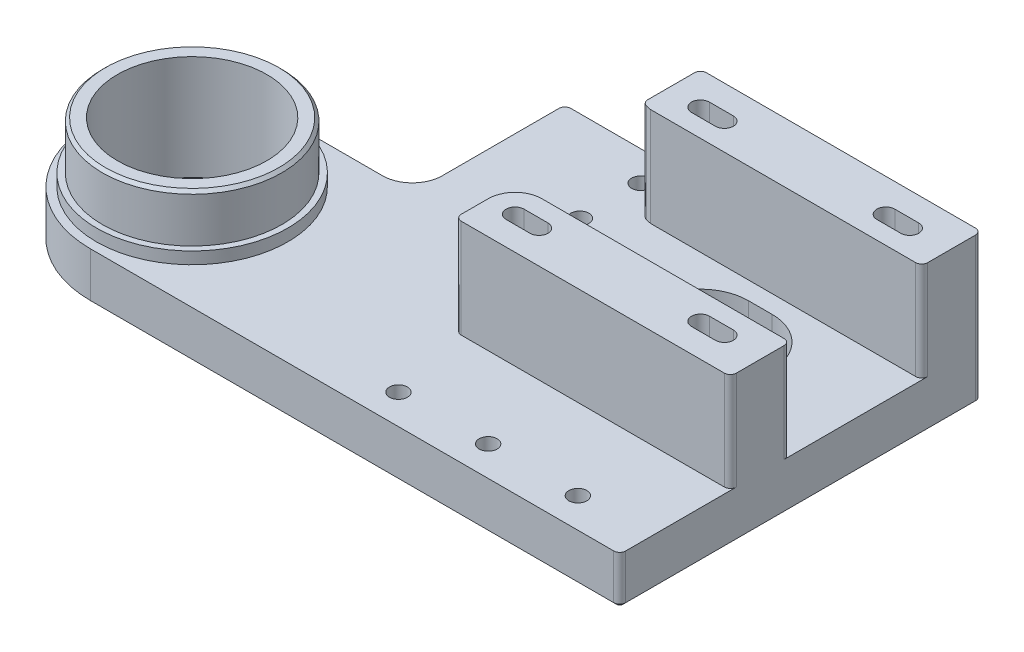
SolidWorks part; units mm, degrees
ref_plane "Front Plane" through (0, 0, 0) normal (0, 0, 1) x (1, 0, 0)
ref_plane "Top Plane" through (0, 0, 0) normal (0, 1, 0) x (1, 0, 0)
ref_plane "Right Plane" through (0, 0, 0) normal (1, 0, 0) x (0, 0, -1)
sketch "Sketch1" plane through (0, 0, 0) normal (0, 1, 0) x (1, 0, 0)
  line L0 (60.6181, 17.7752) -> (49.3328, 24.1377) construction
  line L2 (-17.5, 17.5) -> (-17.5, -17.5)
  line L5 (47.5, 37.5) -> (78.5, 37.5) construction
  line L6 (47.5, 37.5) -> (47.5, 6.5) construction
  line L7 (47.5, 6.5) -> (78.5, 6.5) construction
  line L8 (78.5, 37.5) -> (78.5, 6.5) construction
  line L9 (64.0945, 26.7249) -> (9.1398, 39.4552) construction
  line L10 (42.2652, 20.3799) -> (40.3703, -3.2389) construction
  line L11 (63, 22) -> (63, 43) construction
  line L12 (84, 43) -> (42, 43) construction
  line L13 (84, 43) -> (84, 1) construction
  line L14 (84, 1) -> (42, 1) construction
  line L15 (42, 43) -> (42, 1) construction
  line L16 (63, 22) -> (84, 22) construction
  line L17 (-12.5, -1000) -> (-12.5, 49000) construction
  line L18 (-1001.6818, 12.5) -> (48998.3182, 12.5) construction
  line L19 (-991.5, -12.5) -> (49008.5, -12.5) construction
  line L20 (-17.5, -17.5) -> (89, -17.5)
  line L21 (89, 43) -> (89, -17.5)
  line L23 (47.5, 37.5) -> (51.5, 37.5) construction
  line L24 (47.5, 39) -> (51.5, 39)
  line L25 (47.5, 36) -> (51.5, 36)
  line L26 (78.5, 37.5) -> (82.5, 37.5) construction
  line L27 (78.5, 39) -> (82.5, 39)
  line L28 (78.5, 36) -> (82.5, 36)
  line L29 (47.5, 6.5) -> (51.5, 6.5) construction
  line L30 (47.5, 8) -> (51.5, 8)
  line L31 (47.5, 5) -> (51.5, 5)
  line L32 (78.5, 6.5) -> (82.5, 6.5) construction
  line L33 (78.5, 8) -> (82.5, 8)
  line L34 (78.5, 5) -> (82.5, 5)
  line L35 (63, 22) -> (67, 22) construction
  line L36 (63, 30) -> (67, 30)
  line L37 (63, 14) -> (67, 14)
  line L40 (-17.5, 17.5) -> (19.3317, 17.5)
  line L41 (19.3317, 17.5) -> (19.3317, 43)
  line L42 (19.3317, 43) -> (89, 43)
  line L43 (84, -966.1083) -> (84, 49033.8917) construction
  line L44 (19.3317, 43) -> (-79.4, 43) construction
  line L45 (19.3317, 38) -> (89, 38) construction
  circle A0 centre (0, 0) radius 21 construction
  circle A1 centre (47.5, 37.5) radius 1.5 construction
  circle A2 centre (78.5, 37.5) radius 1.5 construction
  circle A3 centre (78.5, 6.5) radius 1.5 construction
  circle A4 centre (47.5, 6.5) radius 1.5 construction
  circle A5 centre (63, 22) radius 8 construction
  circle A9 centre (47, 20) radius 1.425
  circle A10 centre (47, 20) radius 6.5 construction
  circle A11 centre (0, 0) radius 42 construction
  arc A12 (40.3703, -3.2389) -> (9.1398, 39.4552) centre (0, 0) cw construction
  arc A13 (42.2652, 20.3799) -> (49.3328, 24.1377) centre (47, 20) cw construction
  arc A14 (64.0945, 26.7249) -> (60.6181, 17.7752) centre (63, 22) cw construction
  circle A15 centre (63, 22) radius 7 construction
  arc A16 (47.5, 39) -> (47.5, 36) centre (47.5, 37.5) ccw
  arc A17 (51.5, 36) -> (51.5, 39) centre (51.5, 37.5) ccw
  arc A18 (78.5, 39) -> (78.5, 36) centre (78.5, 37.5) ccw
  arc A19 (82.5, 36) -> (82.5, 39) centre (82.5, 37.5) ccw
  arc A20 (47.5, 8) -> (47.5, 5) centre (47.5, 6.5) ccw
  arc A21 (51.5, 5) -> (51.5, 8) centre (51.5, 6.5) ccw
  arc A22 (78.5, 8) -> (78.5, 5) centre (78.5, 6.5) ccw
  arc A23 (82.5, 5) -> (82.5, 8) centre (82.5, 6.5) ccw
  arc A24 (63, 30) -> (63, 14) centre (63, 22) ccw
  arc A25 (67, 14) -> (67, 30) centre (67, 22) ccw
  circle A26 centre (0, 0) radius 12.5
  circle A27 centre (47, -12.5) radius 1.5
  circle A28 centre (62, -12.5) radius 1.5
  circle A29 centre (77, -12.5) radius 1.5
  circle A30 centre (37, 38) radius 1.5
  circle A31 centre (37, 27.8373) radius 1.5
  point P17 (47.5, 22)
  point P18 (63, 37.5)
  point P19 (49.5, 37.5)
  point P27 (63, 43)
  point P47 (80.5, 37.5)
  point P56 (49.5, 6.5)
  point P62 (80.5, 6.5)
  point P68 (65, 22)
  dimension "D1" = 42
  dimension "D2" = 16
  dimension "D4" = 3
  dimension "D5" = 40.5
  dimension "D6" = 4.85
  dimension "D7" = 4.75
  dimension "D9" = 2.85
  dimension "D14" = 13
  dimension "D15" = 84
  dimension "D13" = 14
  dimension "D18" = 25
  dimension "D23" = 3
  dimension "D3" = 31
  dimension "D8" = 42
  dimension "D10" = 5
  dimension "D11" = 5
  dimension "D12" = 5
  dimension "D16" = 4
  dimension "D17" = 5
  dimension "D19" = 63
  dimension "D20" = 44
  dimension "D21" = 20
  dimension "D22" = 47
  dimension "D24" = 5
  dimension "D26" = 5
  dimension "D27" = 5
  dimension "D25" = 3
extrude "Boss-Extrude1" add sketch "Sketch1" along normal blind 8
sketch "Sketch11" plane through (0, 0, 0) normal (0, -1, 0) x (1, 0, 0)
  circle A0 centre (47, 12.5) radius 3
  circle A1 centre (62, 12.5) radius 3
  circle A2 centre (77, 12.5) radius 3
  circle A4 centre (37, -27.8373) radius 3
  circle A5 centre (37, -38) radius 3
  point P5 (62, 12.5)
  point P9 (77, 12.5)
  point P13 (47, -20)
  point P17 (37, -27.8373)
  point P19 (37, -38)
  dimension "D1" = 6
extrude "Cut-Extrude1" cut sketch "Sketch11" against normal blind 2
chamfer "Chamfer6" distance 0.5 angle 70 5 edges at (77, 2, 9.5) (37, 2, -41) (37, 2, -30.8373) (62, 2, 9.5) (47, 2, 9.5) first distance on face at (77, 2, 9.5) first distance on face at (37, 2, -41) first distance on face at (37, 2, -30.8373) first distance on face at (62, 2, 9.5) first distance on face at (47, 2, 9.5)
sketch "Sketch12" plane through (0, 0, 0) normal (0, -1, 0) x (1, 0, 0)
  line L0 (47.5, -6.5) -> (51.5, -6.5) construction
  line L1 (47.5, -3) -> (51.5, -3)
  line L2 (47.5, -10) -> (51.5, -10)
  line L3 (78.5, -6.5) -> (82.5, -6.5) construction
  line L4 (78.5, -3) -> (82.5, -3)
  line L5 (78.5, -10) -> (82.5, -10)
  line L6 (47.5, -37.5) -> (51.5, -37.5) construction
  line L7 (47.5, -34) -> (51.5, -34)
  line L8 (47.5, -41) -> (51.5, -41)
  line L9 (78.5, -37.5) -> (82.5, -37.5) construction
  line L10 (78.5, -34) -> (82.5, -34)
  line L11 (78.5, -41) -> (82.5, -41)
  arc A0 (47.5, -3) -> (47.5, -10) centre (47.5, -6.5) ccw
  arc A1 (51.5, -10) -> (51.5, -3) centre (51.5, -6.5) ccw
  arc A2 (78.5, -3) -> (78.5, -10) centre (78.5, -6.5) ccw
  arc A3 (82.5, -10) -> (82.5, -3) centre (82.5, -6.5) ccw
  arc A4 (47.5, -34) -> (47.5, -41) centre (47.5, -37.5) ccw
  arc A5 (51.5, -41) -> (51.5, -34) centre (51.5, -37.5) ccw
  arc A6 (78.5, -34) -> (78.5, -41) centre (78.5, -37.5) ccw
  arc A7 (82.5, -41) -> (82.5, -34) centre (82.5, -37.5) ccw
  point P4 (49.5, -6.5)
  point P13 (80.5, -6.5)
  point P18 (49.5, -37.5)
  point P27 (80.5, -37.5)
  dimension "D1" = 3.5
extrude "Cut-Extrude2" cut sketch "Sketch12" against normal blind 2
chamfer "Chamfer7" distance 0.5 angle 70 16 edges at (86, 2, -37.5) (80.5, 2, -34) (80.5, 2, -41) (75, 2, -37.5) (55, 2, -37.5) (49.5, 2, -34) (49.5, 2, -41) (44, 2, -37.5) (86, 2, -6.5) (80.5, 2, -3) (80.5, 2, -10) (75, 2, -6.5) (55, 2, -6.5) (49.5, 2, -3) (49.5, 2, -10) (44, 2, -6.5) first distance on face at (84.25, 1, -37.5) first distance on face at (80.5, 1, -34) first distance on face at (80.5, 1, -41) first distance on face at (76.75, 1, -37.5) first distance on face at (53.25, 1, -37.5) first distance on face at (49.5, 1, -34) first distance on face at (49.5, 1, -41) first distance on face at (45.75, 1, -37.5) first distance on face at (84.25, 1, -6.5) first distance on face at (80.5, 1, -3) first distance on face at (80.5, 1, -10) first distance on face at (76.75, 1, -6.5) first distance on face at (53.25, 1, -6.5) first distance on face at (49.5, 1, -3) first distance on face at (49.5, 1, -10) first distance on face at (45.75, 1, -6.5)
sketch "Sketch2" plane through (0, 8, 0) normal (0, -1, 0) x (1, 0, 0)
  circle A0 centre (0, 0) radius 12.5 construction
  circle A2 centre (0, 0) radius 16
  circle A5 centre (0, 0) radius 12.5
  point P5 (0, 0)
  dimension "D1" = 32
extrude "Boss-Extrude2" add sketch "Sketch2" against normal blind 2
sketch "Sketch6" plane through (0, 10, 0) normal (0, 1, 0) x (1, 0, 0)
  circle A2 centre (0, 0) radius 15
  circle A3 centre (0, 0) radius 12.5 construction
  circle A4 centre (0, 0) radius 12.5
  point P5 (-1.1044, 0)
  dimension "D1" = 30
sketch "Sketch5" plane through (0, 8, 0) normal (0, 1, 0) x (1, 0, 0)
  circle A0 centre (47, 20) radius 1.425 construction
  circle A1 centre (47, 20) radius 1.425
  circle A2 centre (47, 20) radius 3.425
  dimension "D1" = 2
extrude "Boss-Extrude3" add sketch "Sketch5" along normal blind 2.5
chamfer "Chamfer3" distance 1 angle 45 1 edges at (47, 10.5, -16.575)
sketch "Sketch7" plane through (0, 8, 0) normal (0, 1, 0) x (1, 0, 0)
  line L0 (78.5, 2) -> (82.5, 2)
  line L1 (82.5, 11) -> (78.5, 11)
  line L2 (78.5, 5) -> (82.5, 5)
  line L3 (82.5, 8) -> (78.5, 8)
  line L4 (78.5, 5) -> (82.5, 5)
  line L5 (82.5, 8) -> (78.5, 8)
  line L6 (47.5, 5) -> (51.5, 5)
  line L7 (51.5, 8) -> (47.5, 8)
  line L8 (47.5, 5) -> (51.5, 5)
  line L9 (51.5, 8) -> (47.5, 8)
  line L10 (78.5, 36) -> (82.5, 36)
  line L11 (82.5, 39) -> (78.5, 39)
  line L12 (78.5, 36) -> (82.5, 36)
  line L13 (82.5, 39) -> (78.5, 39)
  line L14 (47.5, 36) -> (51.5, 36)
  line L15 (51.5, 39) -> (47.5, 39)
  line L16 (47.5, 36) -> (51.5, 36)
  line L17 (51.5, 39) -> (47.5, 39)
  line L18 (47.5, 2) -> (51.5, 2)
  line L19 (51.5, 11) -> (47.5, 11)
  line L20 (78.5, 33) -> (82.5, 33)
  line L21 (82.5, 42) -> (78.5, 42)
  line L22 (47.5, 33) -> (51.5, 33)
  line L23 (51.5, 42) -> (47.5, 42)
  arc A4 (82.5, 2) -> (82.5, 11) centre (82.5, 6.5) ccw
  arc A5 (78.5, 11) -> (78.5, 2) centre (78.5, 6.5) ccw
  arc A6 (78.5, 8) -> (78.5, 5) centre (78.5, 6.5) ccw
  arc A7 (82.5, 5) -> (82.5, 8) centre (82.5, 6.5) ccw
  arc A8 (78.5, 8) -> (78.5, 5) centre (78.5, 6.5) ccw
  arc A9 (82.5, 5) -> (82.5, 8) centre (82.5, 6.5) ccw
  arc A10 (47.5, 8) -> (47.5, 5) centre (47.5, 6.5) ccw
  arc A11 (51.5, 5) -> (51.5, 8) centre (51.5, 6.5) ccw
  arc A12 (47.5, 8) -> (47.5, 5) centre (47.5, 6.5) ccw
  arc A13 (51.5, 5) -> (51.5, 8) centre (51.5, 6.5) ccw
  arc A14 (78.5, 39) -> (78.5, 36) centre (78.5, 37.5) ccw
  arc A15 (82.5, 36) -> (82.5, 39) centre (82.5, 37.5) ccw
  arc A16 (78.5, 39) -> (78.5, 36) centre (78.5, 37.5) ccw
  arc A17 (82.5, 36) -> (82.5, 39) centre (82.5, 37.5) ccw
  arc A18 (47.5, 39) -> (47.5, 36) centre (47.5, 37.5) ccw
  arc A19 (51.5, 36) -> (51.5, 39) centre (51.5, 37.5) ccw
  arc A20 (47.5, 39) -> (47.5, 36) centre (47.5, 37.5) ccw
  arc A21 (51.5, 36) -> (51.5, 39) centre (51.5, 37.5) ccw
  arc A22 (51.5, 2) -> (51.5, 11) centre (51.5, 6.5) ccw
  arc A23 (47.5, 11) -> (47.5, 2) centre (47.5, 6.5) ccw
  arc A24 (82.5, 33) -> (82.5, 42) centre (82.5, 37.5) ccw
  arc A25 (78.5, 42) -> (78.5, 33) centre (78.5, 37.5) ccw
  arc A26 (51.5, 33) -> (51.5, 42) centre (51.5, 37.5) ccw
  arc A27 (47.5, 42) -> (47.5, 33) centre (47.5, 37.5) ccw
  dimension "D1" = 0
  dimension "D2" = 0
  dimension "D3" = 0
  dimension "D4" = 0
  dimension "D5" = 3
extrude "Boss-Extrude5" add sketch "Sketch7" along normal blind 16.5
sketch "Sketch10" plane through (0, 8, 0) normal (0, 1, 0) x (1, 0, 0)
  line L0 (42, 33.3828) -> (42, 43)
  line L1 (19.3317, 43) -> (89, 43) construction
  line L2 (42, 43) -> (89, 43)
  line L3 (89, 43) -> (89, 38)
  line L4 (89, 38) -> (89, 33)
  line L5 (89, 43) -> (89, -17.5) construction
  line L6 (89, 33) -> (43.6526, 33)
  line L7 (47.5, 39) -> (51.5, 39) construction
  line L8 (47.5, 36) -> (51.5, 36) construction
  line L9 (47.5, 39) -> (51.5, 39)
  line L10 (47.5, 36) -> (51.5, 36)
  line L11 (78.5, 39) -> (82.5, 39) construction
  line L12 (78.5, 36) -> (82.5, 36) construction
  line L13 (78.5, 39) -> (82.5, 39)
  line L14 (78.5, 36) -> (82.5, 36)
  line L15 (47.5, 11) -> (89, 11)
  line L16 (89, 11) -> (89, 1)
  line L17 (89, 1) -> (42.9884, 1)
  line L18 (47.5, 5) -> (51.5, 5) construction
  line L19 (47.5, 8) -> (51.5, 8) construction
  line L20 (47.5, 5) -> (51.5, 5)
  line L21 (47.5, 8) -> (51.5, 8)
  line L22 (78.5, 5) -> (82.5, 5) construction
  line L23 (78.5, 8) -> (82.5, 8) construction
  line L24 (78.5, 5) -> (82.5, 5)
  line L25 (78.5, 8) -> (82.5, 8)
  line L26 (42, 43) -> (42, 1) construction
  line L27 (84, 1) -> (42, 1) construction
  line L30 (64.433, 28.1862) -> (9.4784, 40.9165)
  line L31 (64.433, 28.1862) -> (9.4784, 40.9165) construction
  line L32 (63.756, 25.2636) -> (8.8013, 37.9939)
  line L33 (63.756, 25.2636) -> (8.8013, 37.9939) construction
  line L35 (47.5, 33) -> (51.5, 33) construction
  line L36 (43.6526, 33) -> (42, 33.3828)
  line L38 (42.9884, 1) -> (43, 6.5095)
  line L39 (40.77, 20.4998) -> (38.8751, -3.1189)
  line L40 (40.77, 20.4998) -> (38.8751, -3.1189) construction
  line L41 (43.7604, 20.2599) -> (41.8655, -3.3589)
  line L42 (43.7604, 20.2599) -> (41.8655, -3.3589) construction
  arc A2 (51.5, 36) -> (51.5, 39) centre (51.5, 37.5) ccw construction
  arc A3 (47.5, 39) -> (47.5, 36) centre (47.5, 37.5) ccw construction
  arc A4 (51.5, 36) -> (51.5, 39) centre (51.5, 37.5) ccw
  arc A5 (47.5, 39) -> (47.5, 36) centre (47.5, 37.5) ccw
  arc A6 (82.5, 36) -> (82.5, 39) centre (82.5, 37.5) ccw construction
  arc A7 (78.5, 39) -> (78.5, 36) centre (78.5, 37.5) ccw construction
  arc A8 (82.5, 36) -> (82.5, 39) centre (82.5, 37.5) ccw
  arc A9 (78.5, 39) -> (78.5, 36) centre (78.5, 37.5) ccw
  arc A11 (47.5, 8) -> (47.5, 5) centre (47.5, 6.5) ccw construction
  arc A12 (51.5, 5) -> (51.5, 8) centre (51.5, 6.5) ccw construction
  arc A13 (47.5, 8) -> (47.5, 5) centre (47.5, 6.5) ccw
  arc A14 (51.5, 5) -> (51.5, 8) centre (51.5, 6.5) ccw
  arc A15 (78.5, 8) -> (78.5, 5) centre (78.5, 6.5) ccw construction
  arc A16 (82.5, 5) -> (82.5, 8) centre (82.5, 6.5) ccw construction
  arc A17 (78.5, 8) -> (78.5, 5) centre (78.5, 6.5) ccw
  arc A18 (82.5, 5) -> (82.5, 8) centre (82.5, 6.5) ccw
  circle A24 centre (0, 0) radius 43
  circle A25 centre (0, 0) radius 43 construction
  arc A30 (47.5, 11) -> (47.5, 2) centre (47.5, 6.5) ccw construction
  arc A31 (47.5, 11) -> (47.5, 2) centre (47.5, 6.5) ccw construction
  arc A32 (47.5, 11) -> (43, 6.5095) centre (47.5, 6.5) ccw
  dimension "D1" = 1
  dimension "D2" = 1.5
  dimension "D3" = 1.5
  dimension "D4" = 1.5
  dimension "D5" = 1.5
extrude "Boss-Extrude6" add sketch "Sketch10" along normal up to surface (16.5 mm away) up to face at (49.5, 24.5, -6.5)
fillet "Fillet5" radius 18 2 edges at (-17.5, 4, -17.5) (-17.5, 4, 17.5)
extrude "Boss-Extrude4" add sketch "Sketch6" along normal blind 8
fillet "Fillet8" radius 4 1 edges at (47, 8, -16.575)
chamfer "Chamfer5" distance 0.5 angle 45 1 edges at (0, 18, 15)
fillet "Fillet6" radius 5 1 edges at (19.3317, 4, -17.5)
fillet "Fillet9" radius 1 9 edges at (42, 16.25, -43) (42, 16.25, -33.3828) (42.9884, 16.25, -1) (89, 12.25, -43) (89, 16.25, -33) (89, 16.25, -11) (89, 16.25, -1) (19.3317, 4, -43) (89, 4, 17.5)
chamfer "Chamfer2" distance 0.5 angle 45 38 edges at (47, 0, -18.575) (0, 0, 12.5) (44.25, 0, 17.5) (89, 0, -12.75) (75, 0, -22) (65, 0, -30) (65, 0, -14) (55, 0, -22) (54.1658, 0, -43) (19.3317, 0, -32.25) (7.4158, 0, -17.5) (-12.0499, 0, -12.4035) (-12.0499, 0, 12.4035) (17.8672, 0, -18.9645) (88.7071, 0, -42.7071) (88.7071, 0, 17.2071) (19.6246, 0, -42.7071) (47, 0, 9.5) (62, 0, 9.5) (77, 0, 9.5) (37, 0, -41) (37, 0, -30.8373) (55, 0, -6.5) (49.5, 0, -3) (44, 0, -6.5) (49.5, 0, -10) (86, 0, -37.5) (80.5, 0, -34) (75, 0, -37.5) (80.5, 0, -41) (55, 0, -37.5) (49.5, 0, -34) (44, 0, -37.5) (49.5, 0, -41) (86, 0, -6.5) (80.5, 0, -3) (75, 0, -6.5) (80.5, 0, -10)
